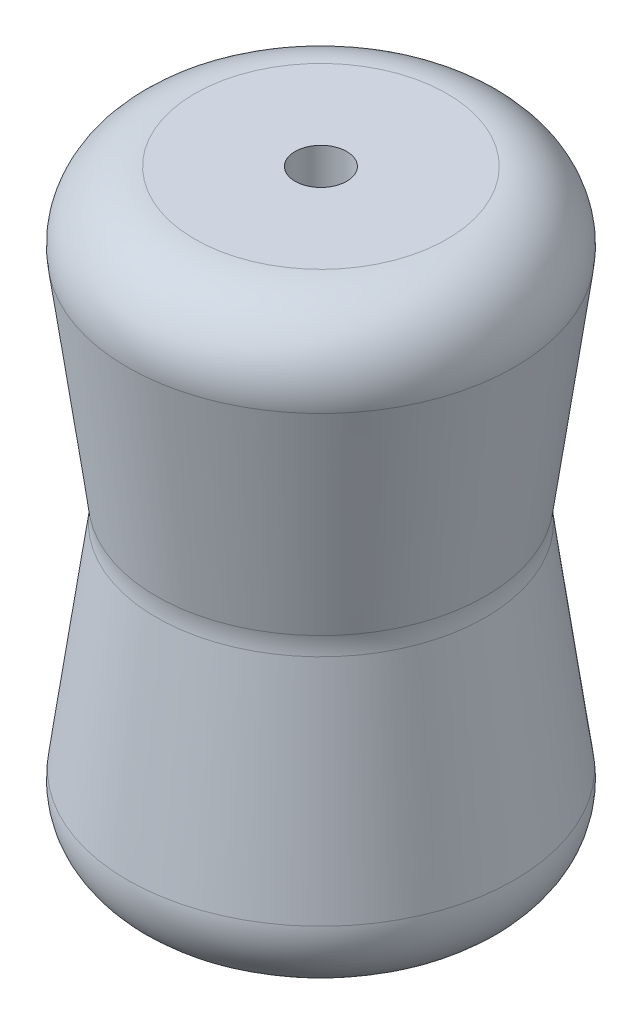
SolidWorks part; units mm, degrees
ref_plane "前视基准面" through (0, 0, 0) normal (0, 0, 1) x (1, 0, 0)
ref_plane "上视基准面" through (0, 0, 0) normal (0, 1, 0) x (1, 0, 0)
ref_plane "右视基准面" through (0, 0, 0) normal (1, 0, 0) x (0, 0, -1)
other "Configuration Table"
sketch "草图2" plane through (0, 0, 0) normal (0, 0, 1) x (1, 0, 0)
  line L0 (0, 0) -> (0, 44)
  line L1 (0, 22) -> (-12, 22) construction
  line L2 (-12, 22) -> (-15, 0)
  line L3 (-15, 0) -> (0, 0)
  line L4 (-12, 22) -> (-15, 44)
  line L5 (-15, 44) -> (0, 44)
  dimension "D1" = 15
  dimension "D2" = 12
  dimension "D3" = 22
revolve "旋转1" add sketch "草图2" angle 360 about L0 region at (-6.7778, 10.5926, 0)
sketch "草图3" plane through (0, 0, 0) normal (0, -1, 0) x (1, 0, 0)
  circle A0 centre (0, 0) radius 1.9
  dimension "D1" = 3.8
extrude "切除-拉伸1" cut sketch "草图3" against normal blind 60
fillet "圆角1" radius 5 3 edges at (15, 0, 0) (12, 22, 0) (15, 44, 0)
